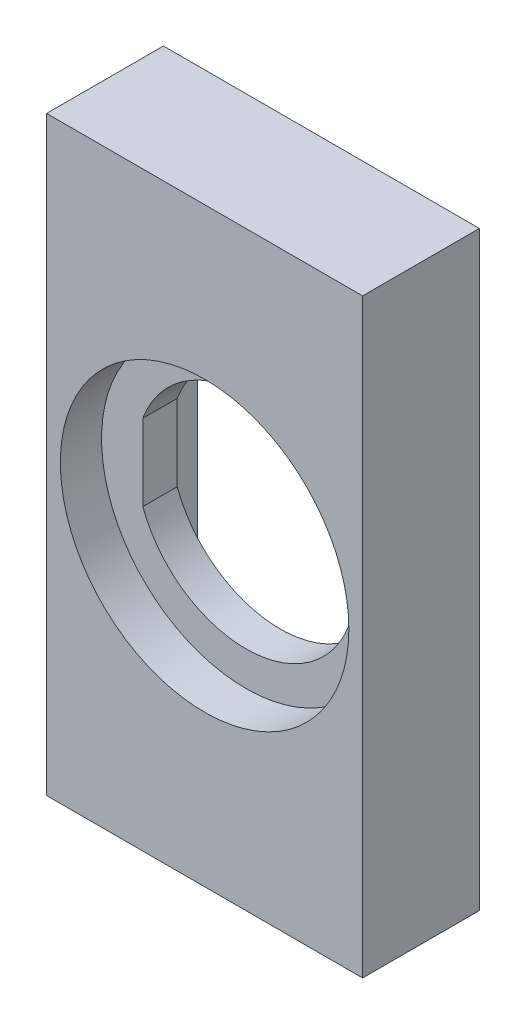
SolidWorks part; units mm, degrees
ref_plane "Plano frontal" through (0, 0, 0) normal (0, 0, 1) x (1, 0, 0)
ref_plane "Plano superior" through (0, 0, 0) normal (0, 1, 0) x (1, 0, 0)
ref_plane "Plano direito" through (0, 0, 0) normal (1, 0, 0) x (0, 0, -1)
sketch "Esboço1" plane through (0, 0, 0) normal (0, 0, 1) x (1, 0, 0)
  line L1 (-11.5, -21.5) -> (11.5, -21.5)
  line L2 (-11.5, -21.5) -> (-11.5, 21.5)
  line L3 (-11.5, 21.5) -> (11.5, 21.5)
  line L4 (11.5, -21.5) -> (11.5, 21.5)
  line L5 (-11.5, -21.5) -> (11.5, 21.5) construction
  line L6 (-11.5, 21.5) -> (11.5, -21.5) construction
  point P0 (0, 0)
  dimension "D1" = 23
  dimension "D2" = 43
extrude "Ressalto-extrusão1" add sketch "Esboço1" along normal blind 8.5
sketch "Esboço3" plane through (0, 0, 8.5) normal (0, 0, 1) x (1, 0, 0)
  line L0 (-7.5, 2.7839) -> (-7.5, -2.7839)
  line L1 (7.5, 2.7839) -> (7.5, -2.7839)
  arc A0 (-7.5, -2.7839) -> (7.5, -2.7839) centre (0, 0) ccw
  arc A1 (7.5, 2.7839) -> (-7.5, 2.7839) centre (0, 0) ccw
  dimension "D1" = 16
  dimension "D2" = 7.5
  dimension "D3" = 7.5
extrude "Corte-extrusão2" cut sketch "Esboço3" against normal through all
sketch "Esboço5" plane through (0, 0, 8.5) normal (0, 0, 1) x (1, 0, 0)
  circle A0 centre (0, 0) radius 10.5
  dimension "D1" = 21
extrude "Corte-extrusão4" cut sketch "Esboço5" against normal blind 3
sketch "Esboço6" plane through (0, 0, 0) normal (0, 0, -1) x (-1, 0, 0)
  line L0 (-11.5, -21.5) -> (-11.5, 21.5) construction
  line L1 (-9, -19) -> (9, -19)
  line L2 (-9, -19) -> (-9, 19)
  line L3 (-9, 19) -> (9, 19)
  line L4 (9, -19) -> (9, 19)
  line L5 (-9, -19) -> (9, 19) construction
  line L6 (-9, 19) -> (9, -19) construction
  line L7 (-11.5, 21.5) -> (11.5, 21.5) construction
  point P0 (0, 0)
  dimension "D1" = 2.5
  dimension "D2" = 2.5
extrude "Corte-extrusão5" cut sketch "Esboço6" against normal blind 3
sketch "Esboço7" plane through (0, 0, 3) normal (0, 0, -1) x (-1, 0, 0)
  line L0 (-9, -19) -> (-9, -6.3246)
  line L1 (-9, 19) -> (9, 19)
  line L2 (9, 19) -> (9, 6.3246)
  line L3 (9, -19) -> (-9, -19)
  line L4 (-9, 6.3246) -> (-9, 19)
  line L5 (9, -6.3246) -> (9, -19)
  arc A0 (-9, -6.3246) -> (9, -6.3246) centre (0, 0) ccw
  arc A1 (9, 6.3246) -> (-9, 6.3246) centre (0, 0) ccw
  dimension "D1" = 22
extrude "Corte-extrusão6" cut sketch "Esboço7" against normal blind 1
